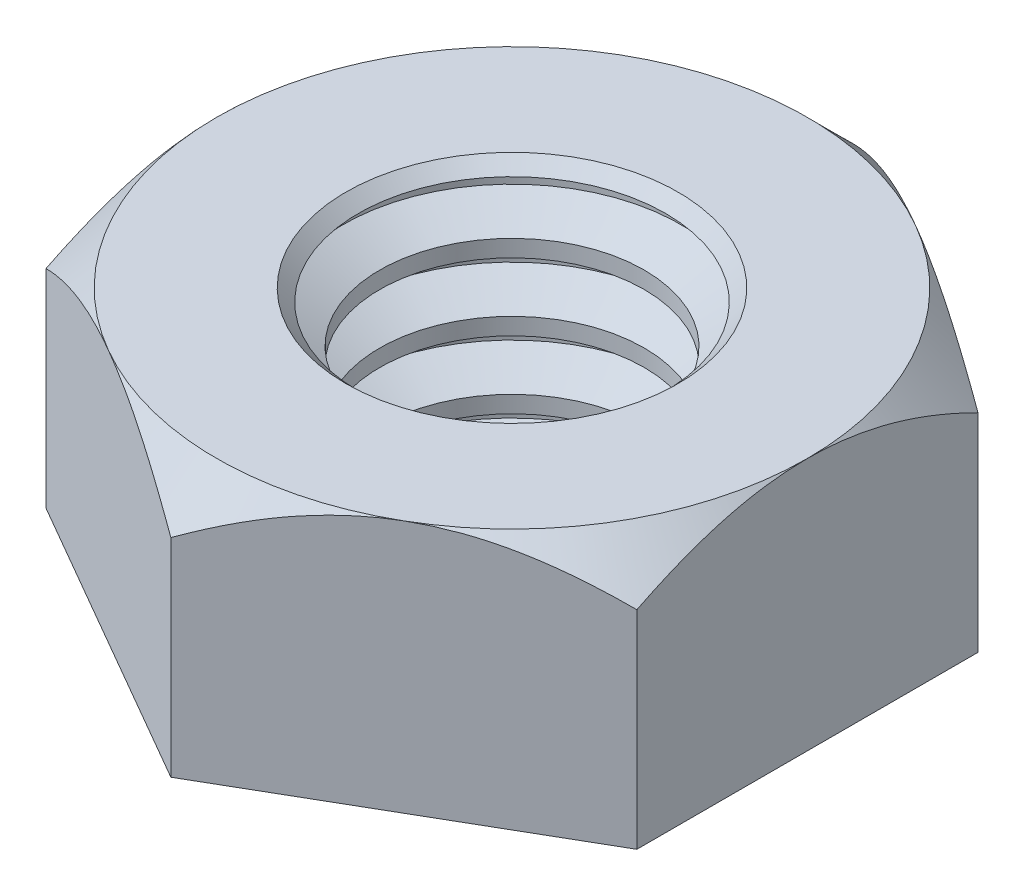
SolidWorks part; units mm, degrees
material "Plain Carbon Steel"
ref_plane "Front" through (0, 0, 0) normal (0, 0, 1) x (1, 0, 0)
ref_plane "Top" through (0, 0, 0) normal (0, 1, 0) x (1, 0, 0)
ref_plane "Right" through (0, 0, 0) normal (1, 0, 0) x (0, 0, -1)
sketch "Sketch1" plane through (0, 0, 0) normal (0, 1, 0) x (1, 0, 0)
  line L1 (0, 6.4158) -> (-5.5563, 3.2079)
  line L2 (-5.5563, 3.2079) -> (-5.5563, -3.2079)
  line L3 (-5.5563, -3.2079) -> (0, -6.4158)
  line L4 (0, -6.4158) -> (5.5562, -3.2079)
  line L5 (5.5562, -3.2079) -> (5.5562, 3.2079)
  line L6 (5.5562, 3.2079) -> (0, 6.4158)
  circle A0 centre (0, 0) radius 5.5563 construction
  dimension "Hex Flats" = 11.1125
extrude "Extrude1" add sketch "Sketch1" along normal blind 4.7625
sketch "Sketch3" plane through (0, 0, 0) normal (1, 0, 0) x (0, 0, -1)
  line L0 (5.5562, 4.7625) -> (6.4158, 3.9029)
  line L1 (3.2079, 4.7625) -> (6.4158, 4.7625) construction
  line L2 (6.4158, 4.7625) -> (6.4158, 0) construction
  line L3 (6.4158, 3.9029) -> (6.4158, 4.7625)
  line L4 (6.4158, 4.7625) -> (5.5562, 4.7625)
  line L5 (0, 0.542) -> (0, -0.542) construction
  dimension "D1" = 45
  dimension "D2" = 11.1125
revolve "Cut-Revolve2" cut sketch "Sketch3" angle 360 about L5
sketch "Sketch2" plane through (0, 0, 0) normal (0, 0, 1) x (1, 0, 0)
  line L0 (0, 1.6636) -> (0, -0.3796) construction
  line L1 (0, 4.7625) -> (2.4876, 4.7625)
  line L3 (0, 4.7625) -> (5.5562, 4.7625) construction
  line L4 (0, 3.4925) -> (2.4876, 3.4925)
  line L5 (2.4876, 4.7625) -> (3.175, 4.3656)
  line L6 (3.175, 4.3656) -> (3.175, 4.2069)
  line L7 (3.175, 4.2069) -> (2.4876, 3.81)
  line L9 (2.4876, 3.4925) -> (2.4876, 3.81)
  line L10 (0, 3.4925) -> (0, 4.7625)
  line L11 (2.4876, 4.7625) -> (2.4876, 3.81) construction
  line L12 (3.175, 4.2862) -> (2.4876, 4.2862) construction
  dimension "D1" = 60
  dimension "D2" = 0.3175
  dimension "D5" = 0.1588
  dimension "Pitch" = 1.27
  dimension "Major Dia." = 6.35
revolve "Cut-Revolve1" cut sketch "Sketch2" angle 360 about L0
pattern_linear "LPattern2" count 4 spacing 1.27 along (0, -1, 0) of "Cut-Revolve1"
chamfer "Chamfer1" distance 0.635 angle 45 1 edges at (0, 4.7625, 2.4876) first distance on face at (0, 4.7625, 0)
equation "\"D5@Sketch2\"=\"Pitch@Sketch2\"/8"
equation "\"D2@Sketch2\"=\"Pitch@Sketch2\"/4"
equation "\"D3@LPattern2\"=\"Pitch@Sketch2\""
equation "\"D1@LPattern2\"=int(\"Height@Extrude1\"/\"Pitch@Sketch2\")+1"
equation "\"D2@Sketch3\"=\"Hex Flats@Sketch1\""
equation "\"D1@Chamfer1\"=\"Pitch@Sketch2\"/2"
